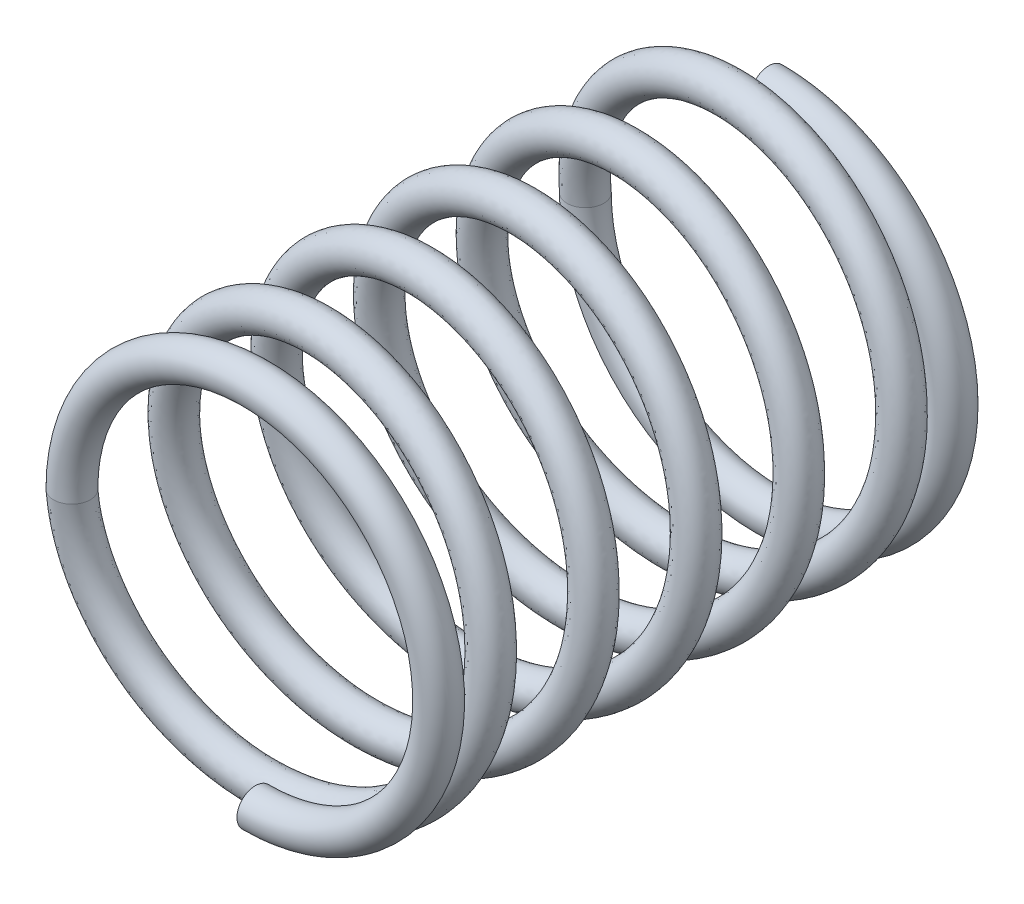
SolidWorks part; units mm, degrees
ref_plane "Alzado" through (0, 0, 0) normal (0, 0, 1) x (1, 0, 0)
ref_plane "Planta" through (0, 0, 0) normal (0, 1, 0) x (1, 0, 0)
ref_plane "Vista lateral" through (0, 0, 0) normal (1, 0, 0) x (0, 0, -1)
sketch "Croquis1" plane through (0, 0, 0) normal (0, 0, 1) x (1, 0, 0)
  circle A0 centre (0, 0) radius 5
  dimension "D1" = 10
curve "Hélice/Espiral1" pitch 2.8 height 14 radius 5 left hand yes centre (0, 0, 0) axis (0, 0, 1) start towards (-1, 0, 0)
sketch "Croquis2" plane through (0, 0, 0) normal (0, 1, 0) x (1, 0, 0)
  circle A0 centre (-5, 0) radius 0.5
  spline S0 degree 3 poles (-5, 0) (-5, -0.058) (-4.7397, -0.1752) (-3.6276, -0.35) (-1.9632, -0.525) (0, -0.7) (1.9632, -0.875) (3.6276, -1.05) (4.7397, -1.225) (5.1302, -1.4) (4.7397, -1.575) (3.6276, -1.75) (1.9632, -1.925) (0, -2.1) (-1.9632, -2.275) (-3.6276, -2.45) (-4.7397, -2.625) (-5.1302, -2.8) (-4.7397, -2.975) (-3.6276, -3.15) (-1.9632, -3.325) (0, -3.5) (1.9632, -3.675) (3.6276, -3.85) (4.7397, -4.025) (5.1302, -4.2) (4.7397, -4.375) (3.6276, -4.55) (1.9632, -4.725) (0, -4.9) (-1.9632, -5.075) (-3.6276, -5.25) (-4.7397, -5.425) (-5.1302, -5.6) (-4.7397, -5.775) (-3.6276, -5.95) (-1.9632, -6.125) (0, -6.3) (1.9632, -6.475) (3.6276, -6.65) (4.7397, -6.825) (5.1302, -7) (4.7397, -7.175) (3.6276, -7.35) (1.9632, -7.525) (0, -7.7) (-1.9632, -7.875) (-3.6276, -8.05) (-4.7397, -8.225) (-5.1302, -8.4) (-4.7397, -8.575) (-3.6276, -8.75) (-1.9632, -8.925) (0, -9.1) (1.9632, -9.275) (3.6276, -9.45) (4.7397, -9.625) (5.1302, -9.8) (4.7397, -9.975) (3.6276, -10.15) (1.9632, -10.325) (0, -10.5) (-1.9632, -10.675) (-3.6276, -10.85) (-4.7397, -11.025) (-5.1302, -11.2) (-4.7397, -11.375) (-3.6276, -11.55) (-1.9632, -11.725) (0, -11.9) (1.9632, -12.075) (3.6276, -12.25) (4.7397, -12.425) (5.1302, -12.6) (4.7397, -12.775) (3.6276, -12.95) (1.9632, -13.125) (0, -13.3) (-1.9632, -13.475) (-3.6276, -13.65) (-4.7397, -13.8248) (-5, -13.942) (-5, -14) knots 0 0 0 0 0.0125 0.025 0.0375 0.05 0.0625 0.075 0.0875 0.1 0.1125 0.125 0.1375 0.15 0.1625 0.175 0.1875 0.2 0.2125 0.225 0.2375 0.25 0.2625 0.275 0.2875 0.3 0.3125 0.325 0.3375 0.35 0.3625 0.375 0.3875 0.4 0.4125 0.425 0.4375 0.45 0.4625 0.475 0.4875 0.5 0.5125 0.525 0.5375 0.55 0.5625 0.575 0.5875 0.6 0.6125 0.625 0.6375 0.65 0.6625 0.675 0.6875 0.7 0.7125 0.725 0.7375 0.75 0.7625 0.775 0.7875 0.8 0.8125 0.825 0.8375 0.85 0.8625 0.875 0.8875 0.9 0.9125 0.925 0.9375 0.95 0.9625 0.975 0.9875 1 1 1 1 construction
  point P3 (-5, 0)
  dimension "D1" = 1
sweep "Barrer1" add profiles "Croquis2" path "Hélice/Espiral1"
sketch "Croquis3" plane through (0, 0, 0) normal (0, 0, 1) x (1, 0, 0)
  line L0 (-4.5, 0) -> (-5.5, 0) construction
  line L1 (0, 0) -> (0, 5) construction
  arc A0 (-5, 0) -> (0, 5) centre (0, 0) ccw
sweep "Barrer2" add profiles "Croquis2<2>" path "Croquis3"
sketch "Croquis2<2>" plane through (0, 0, 0) normal (0, 1, 0) x (1, 0, 0) same geometry as "Croquis2"
ref_plane "Plano1" through (0, 0, 0) normal (0, 1, 0) x (1, 0, 0)
sketch "Croquis5" plane through (0, 0, 0) normal (0, 1, 0) x (1, 0, 0)
  circle A0 centre (-5, -14) radius 0.5 construction
  circle A1 centre (-5, -14) radius 0.5
  point P4 (-5, -14)
ref_plane "Plano2" through (0, 0, 14) normal (0, 0, 1) x (1, 0, 0)
sketch "Croquis6" plane through (0, 0, 14) normal (0, 0, 1) x (1, 0, 0)
  line L0 (0, 0) -> (0, -5) construction
  arc A0 (-5, 0) -> (0, -5) centre (0, 0) cw
sweep "Barrer3" add profiles "Croquis5" path "Croquis6"
ref_axis "Eje1" through (0, 0, -1.25) along (0, 0, 1)
